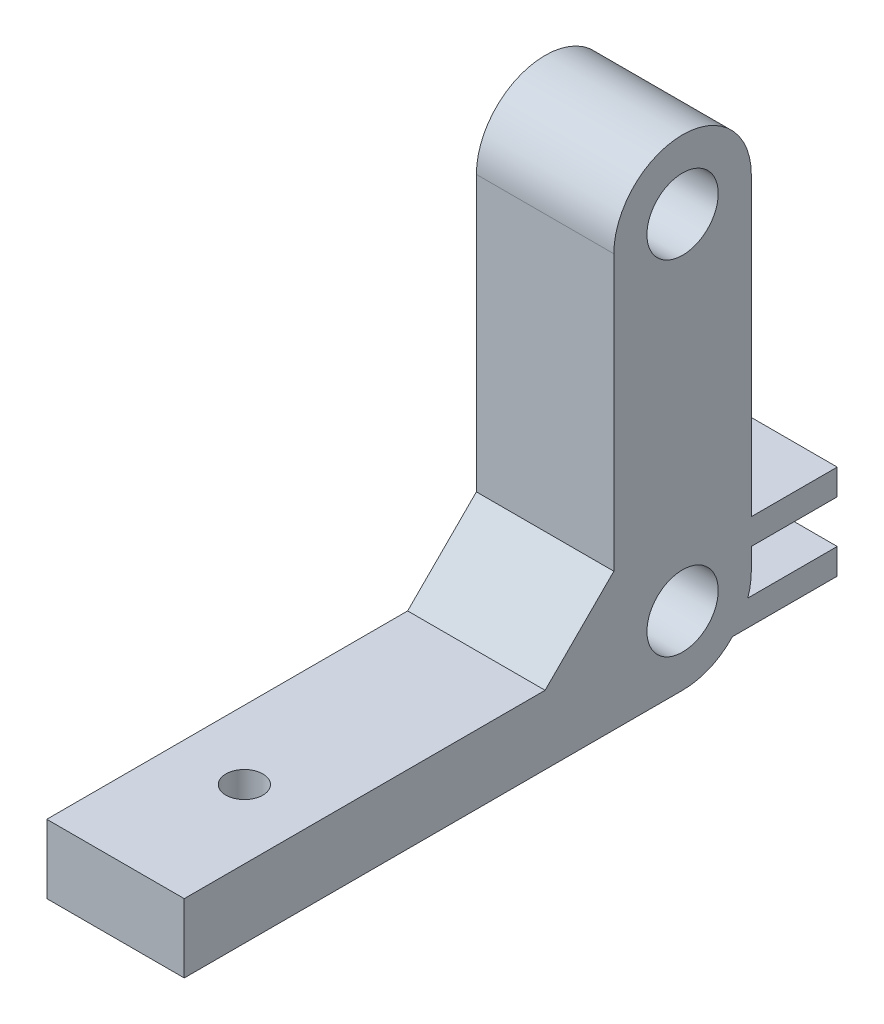
SolidWorks part; units mm, degrees
material "ABS"
ref_plane "Front Plane" through (0, 0, 0) normal (0, 0, 1) x (1, 0, 0)
ref_plane "Top Plane" through (0, 0, 0) normal (0, 1, 0) x (1, 0, 0)
ref_plane "Right Plane" through (0, 0, 0) normal (1, 0, 0) x (0, 0, -1)
sketch "Sketch1" plane through (0, 0, 0) normal (1, 0, 0) x (0, 0, -1)
  line L0 (-10.3091, -58.7899) -> (-58.9824, -58.7899)
  line L1 (7.0176, -45.2899) -> (17.0176, -45.2899)
  line L2 (-8.9824, -10.7899) -> (-8.9824, -42.7899)
  line L3 (-10.3091, -58.7899) -> (-0.9824, -58.7899)
  line L4 (7.0176, -10.7899) -> (7.0176, -45.2899)
  line L5 (-58.9824, -58.7899) -> (-58.9824, -50.7899)
  line L6 (-58.9824, -50.7899) -> (-16.9824, -50.7899)
  line L7 (-8.9824, -42.7899) -> (-16.9824, -50.7899)
  line L8 (17.0176, -45.2899) -> (17.0176, -48.2899)
  line L9 (17.0176, -48.2899) -> (7.0176, -48.2899)
  line L10 (4.8271, -56.2899) -> (17.0176, -56.2899)
  line L11 (17.0176, -56.2899) -> (17.0176, -53.2899)
  line L12 (17.0176, -53.2899) -> (6.617, -53.2899)
  line L13 (7.0176, -48.2899) -> (7.0176, -50.7899)
  circle A0 centre (-0.9824, -10.7899) radius 4.15
  circle A1 centre (-0.9824, -50.7899) radius 4.15
  arc A2 (-8.9824, -10.7899) -> (7.0176, -10.7899) centre (-0.9824, -10.7899) cw
  arc A3 (-0.9824, -58.7899) -> (4.8271, -56.2899) centre (-0.9824, -50.7899) ccw
  arc A4 (6.617, -53.2899) -> (7.0176, -50.7899) centre (-0.9824, -50.7899) ccw
  point P8 (-8.9824, -50.7899)
  dimension "D1" = 8.3
  dimension "D2" = 8.3
  dimension "D4" = 8
  dimension "D11" = 8
  dimension "D3" = 40
  dimension "D5" = 8
  dimension "D6" = 8
  dimension "D7" = 8
  dimension "D8" = 8
  dimension "D9" = 50
  dimension "D10" = 8
  dimension "D12" = 3
  dimension "D14" = 3
  dimension "D15" = 5
  dimension "D16" = 2.5
  dimension "D17" = 10
extrude "Boss-Extrude1" add sketch "Sketch1" against normal blind 16
sketch "Sketch2" plane through (0, -50.7899, 0) normal (0, 1, 0) x (1, 0, 0)
  line L0 (-16, -58.9824) -> (0, -58.9824) construction
  line L1 (0, -16.9824) -> (0, -58.9824) construction
  circle A0 centre (-8, -43.9824) radius 2.15
  dimension "D1" = 4.3
  dimension "D2" = 15
  dimension "D3" = 8
extrude "Cut-Extrude1" cut sketch "Sketch2" against normal through all
ref_point "Point1"
sketch "Sketch3" plane through (0, -45.2899, 0) normal (0, 1, 0) x (1, 0, 0)
  line L0 (-16, 17.0176) -> (0, 17.0176) construction
  line L1 (0, 17.0176) -> (0, 7.0176) construction
  circle A0 centre (-8, 12.0176) radius 1.65
  dimension "D1" = 3.3
  dimension "D2" = 5
  dimension "D3" = 8
extrude "Cut-Extrude2" cut sketch "Sketch3" against normal through all
ref_axis "Z Axis" through (-16.8, 0, 0) along (1, 0, 0)
ref_axis "Y Axis" through (0, 0.0101, 0) along (0, -1, 0)
ref_axis "X Axis" through (0, 0, -20.8176) along (0, 0, 1)
equation "\"rod_diameter\"= 8"
equation "\"D1@Sketch1\"=\"rod_diameter\"+\"printed_hole_tolerance\""
equation "\"D2@Sketch1\"=\"rod_diameter\"+\"printed_hole_tolerance\""
equation "\"D5@Sketch1\"  = \"rod_radius\" + \"rod_hole_thickness\""
equation "\"D6@Sketch1\"  = \"rod_radius\" + \"rod_hole_thickness\""
equation "\"D7@Sketch1\"  = \"rod_radius\" + \"rod_hole_thickness\""
equation "\"rod_hole_thickness\"= 4"
equation "\"D8@Sketch1\"  = \"rod_radius\" + \"rod_hole_thickness\""
equation "\"D4@Sketch1\"  = \"rod_radius\" + \"rod_hole_thickness\""
equation "\"D11@Sketch1\" = \"rod_radius\" + \"rod_hole_thickness\""
equation "\"rod_radius\"= \"rod_diameter\" / 2"
equation "\"D1@Boss-Extrude1\"= \"rod_diameter\" + \"rod_hole_thickness\" * 2"
equation "\"D3@Sketch2\"=\"rod_radius\"+\"rod_hole_thickness\""
equation "\"platter_diameter\"= 320"
equation "\"platter_radius\"= \"platter_diameter\" / 2"
equation "\"extruder_mount_hole_spacing\"= 75"
equation "\"arm_rod_spacing\"= 40"
equation "\"D3@Sketch1\"=\"arm_rod_spacing\""
equation "\"D2@Sketch3\" = \"D17@Sketch1\" / 2"
equation "\"D3@Sketch3\"= \"D1@Boss-Extrude1\" / 2"
equation "\"top_frame_spacing\"= 100"
equation "\"motor_level_rod_spacing\"= 15"
equation "\"linear_bearing_diameter\"= 15"
equation "\"z_rod_spacing\"= 75"
equation "\"z_drive_rod_offset\"= 12"
equation "\"platter_rod_spacing\"= 50"
equation "\"rod_nut_thickness\"= 6.5"
equation "\"rod_nut_inscribed_diameter\"= 13"
equation "\"z_height\"= 400"
equation "\"gear_pitch\"=2"
equation "\"r_gear_teeth\"= 450"
equation "\"theta_gear_teeth\"= 385"
equation "\"sheet_thickness\"=5.333"
equation "\"sheet_tab_hole_thickness\"= \"sheet_thickness\""
equation "\"sheet_tab_width\"= \"sheet_thickness\"*2"
equation "\"sheet_double_tab_width\"= 35"
equation "\"sheet_bolt_diameter\"= 3"
equation "\"sheet_bolt_length\"= 16"
equation "\"sheet_nut_diameter\"= 5.5"
equation "\"sheet_nut_thickness\"= 2.5"
equation "\"sheet_nut_depth\"= 10"
equation "\"bearing_outside_diameter\"= 22"
equation "\"bearing_thickness\"= 7"
equation "\"corner_part_thickness\"= \"sheet_thickness\" + \"bearing_thickness\""
equation "\"setscrew_nut_diameter\"= 6"
equation "\"setscrew_nut_thickness\"= 3"
equation "\"setscrew_bolt_diameter\"= 3"
equation "\"motor_shaft_diameter\"= 5.7"
equation "\"printed_hole_tolerance\"= 0.3"
equation "\"D1@Sketch2\"=4.00 +\"printed_hole_tolerance\""
equation "\"D1@Sketch3\"=\"sheet_bolt_diameter\"+\"printed_hole_tolerance\""
